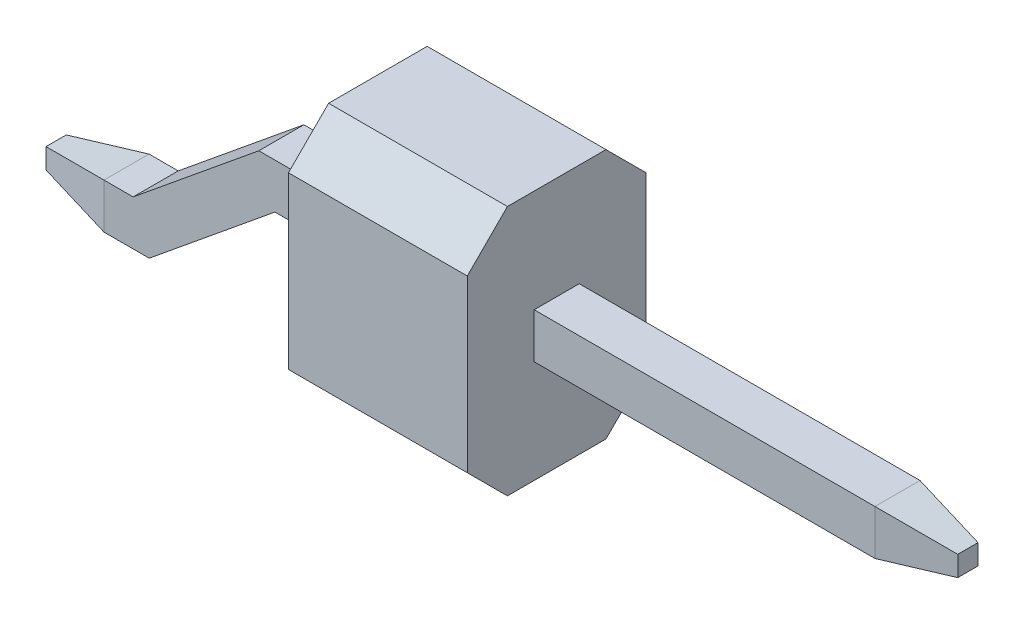
SolidWorks part; units mm, degrees
ref_plane "Front Plane" through (0, 0, 0) normal (0, 0, 1) x (1, 0, 0)
ref_plane "Top Plane" through (0, 0, 0) normal (0, 1, 0) x (1, 0, 0)
ref_plane "Right Plane" through (0, 0, 0) normal (1, 0, 0) x (0, 0, -1)
sketch "Sketch1" plane through (0, 0, 0) normal (0, 1, 0) x (1, 0, 0)
  line L1 (0, 0) -> (2.54, 0)
  line L2 (0, 0) -> (0, 2.54)
  line L3 (0, 2.54) -> (2.54, 2.54)
  line L4 (2.54, 0) -> (2.54, 2.54)
  dimension "D1" = 2.54
  dimension "D2" = 2.54
extrude "Boss-Extrude1" add sketch "Sketch1" along normal blind 3.56
sketch "Sketch2" plane through (2.54, 0, 0) normal (1, 0, 0) x (0, 0, -1)
  line L1 (0.95, 2.1) -> (1.59, 2.1)
  line L2 (0.95, 2.1) -> (0.95, 1.46)
  line L3 (0.95, 1.46) -> (1.59, 1.46)
  line L4 (1.59, 2.1) -> (1.59, 1.46)
  line L5 (1.27, 2.1) -> (1.27, 3.56) construction
  line L6 (0, 3.56) -> (2.54, 3.56) construction
  line L7 (0.95, 1.78) -> (0, 1.78) construction
  line L8 (0, 3.56) -> (0, 0) construction
  line L9 (0, 0) -> (2.54, 0)
  line L10 (2.54, 0) -> (2.54, 3.56)
  line L11 (2.54, 3.56) -> (0, 3.56)
  line L12 (0, 3.56) -> (0, 0)
  line L13 (0, 0) -> (2.54, 0) construction
  line L14 (2.54, 0) -> (2.54, 3.56) construction
  line L15 (2.54, 3.56) -> (0, 3.56) construction
  line L16 (0, 3.56) -> (0, 0) construction
  point P8 (0, 1.78)
  dimension "D2" = 0.64
  dimension "D1" = 0
extrude "Boss-Extrude2" add sketch "Sketch2" along normal blind 5.84
chamfer "Chamfer1" distance 0.57 angle 45 4 edges at (1.27, 0, -2.54) (1.27, 0, 0) (1.27, 3.56, -2.54) (1.27, 3.56, 0)
chamfer "Chamfer2" distance 1 angle 10 4 edges at (8.38, 2.1, -1.27) (8.38, 1.78, -1.59) (8.38, 1.46, -1.27) (8.38, 1.78, -0.95) first distance on face at (5.46, 2.1, -1.27) first distance on face at (5.46, 1.78, -1.59) first distance on face at (5.46, 1.46, -1.27) first distance on face at (5.46, 1.78, -0.95)
sketch "Sketch3" plane through (0, 0, 0) normal (-1, 0, 0) x (0, 0, 1)
  line L0 (-0.95, 2.1) -> (-0.95, 1.46) construction
  line L1 (-0.95, 1.46) -> (-1.59, 1.46) construction
  line L2 (-1.59, 2.1) -> (-0.95, 2.1) construction
  line L3 (-1.59, 1.46) -> (-1.59, 2.1) construction
  line L4 (-0.95, 2.1) -> (-0.95, 1.46)
  line L5 (-0.95, 1.46) -> (-1.59, 1.46)
  line L6 (-1.59, 2.1) -> (-0.95, 2.1)
  line L7 (-1.59, 1.46) -> (-1.59, 2.1)
extrude "Boss-Extrude3" add sketch "Sketch3" along normal blind 2.285
sketch "Sketch4" plane through (-2.285, 0, 0) normal (-1, 0, 0) x (0, 0, 1)
  line L1 (-1.59, 1.46) -> (-0.95, 1.46) construction
  line L2 (-0.95, 0) -> (-1.59, 0)
  line L3 (-0.95, 0) -> (-0.95, 0.64)
  line L4 (-0.95, 0.64) -> (-1.59, 0.64)
  line L5 (-1.59, 0) -> (-1.59, 0.64)
  line L6 (-1.59, 2.1) -> (-1.59, 1.46) construction
  line L7 (-1.97, 0) -> (-0.57, 0) construction
extrude "Boss-Extrude4" add sketch "Sketch4" along normal blind 2.285 separate body
chamfer "Chamfer3" distance 1 angle 10 4 edges at (-4.57, 0, -1.27) (-4.57, 0.32, -1.59) (-4.57, 0.64, -1.27) (-4.57, 0.32, -0.95) first distance on face at (-3.4275, 0, -1.27) first distance on face at (-3.4275, 0.32, -1.59) first distance on face at (-3.4275, 0.64, -1.27) first distance on face at (-3.4275, 0.32, -0.95)
sketch "Sketch5" plane through (0, 0, -1.59) normal (0, 0, -1) x (-1, 0, 0)
  line L1 (2.285, 0.5255) -> (1.1425, 1.46)
  line L2 (2.285, 1.46) -> (0, 1.46) construction
  line L3 (3.1559, 0.64) -> (2.1534, 1.46)
  line L4 (3.3327, 0.4954) -> (1.5477, 1.9554) construction
  line L5 (3.57, 0.64) -> (2.285, 0.64) construction
  line L6 (1.1425, 1.46) -> (2.1534, 1.46)
  line L7 (2.285, 0.64) -> (3.1559, 0.64)
  line L8 (2.285, 0.64) -> (2.285, 0.5255)
  line L9 (2.285, 0.64) -> (2.285, 0) construction
  line L10 (2.285, 0.5255) -> (2.9275, 0) construction
  line L11 (2.9275, 0) -> (1.1425, 1.46) construction
  line L12 (3.57, 0) -> (2.285, 0) construction
  dimension "D1" = 0.64
extrude "Boss-Extrude5" add sketch "Sketch5" against normal up to surface (0.64 mm away) up to face at (-1.1425, 1.78, -0.95)
sketch "Sketch6" plane through (0, 0, -1.59) normal (0, 0, -1) x (-1, 0, 0)
  line L0 (3.1559, 0.64) -> (2.1534, 1.46) construction
  line L1 (2.1534, 1.46) -> (1.3709, 2.1)
  line L2 (2.285, 2.1) -> (0, 2.1) construction
  line L3 (2.285, 2.1) -> (2.285, 1.46) construction
  line L4 (2.285, 1.46) -> (2.1534, 1.46) construction
  line L5 (2.285, 2.1) -> (2.285, 1.46)
  line L6 (2.285, 1.46) -> (2.1534, 1.46)
  line L7 (1.3709, 2.1) -> (2.285, 2.1)
  line L8 (1.1425, 1.46) -> (2.285, 0.5255) construction
  line L9 (2.285, 0.5255) -> (2.9275, 0)
  line L10 (3.57, 0) -> (2.285, 0) construction
  line L11 (2.285, 0.5255) -> (2.285, 0) construction
  line L12 (2.285, 0.5255) -> (2.285, 0)
  line L13 (2.285, 0) -> (2.9275, 0)
extrude "Cut-Extrude1" cut sketch "Sketch6" against normal through all both and the other way through all
